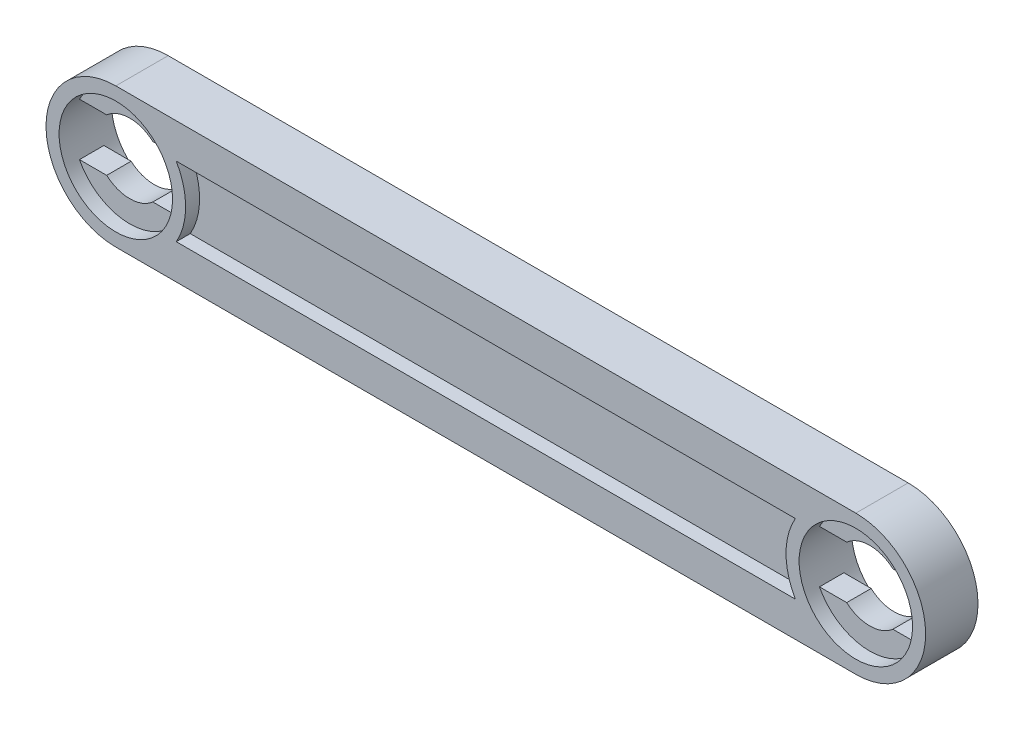
SolidWorks part; units mm, degrees
ref_plane "前视基准面" through (0, 0, 0) normal (0, 0, 1) x (1, 0, 0)
ref_plane "上视基准面" through (0, 0, 0) normal (0, 1, 0) x (1, 0, 0)
ref_plane "右视基准面" through (0, 0, 0) normal (1, 0, 0) x (0, 0, -1)
sketch "草图1" plane through (0, 0, 0) normal (0, 0, 1) x (1, 0, 0)
  line L1 (0, 4) -> (42.4, 4)
  line L3 (0, -4) -> (42.4, -4)
  arc A0 (0, 4) -> (0, -4) centre (0, 0) ccw
  arc A1 (42.4, -4) -> (42.4, 4) centre (42.4, 0) ccw
  dimension "D1" = 42.4
  dimension "D2" = 4
  dimension "D4" = 4
  dimension "D3" = 42.4
extrude "凸台-拉伸1" add sketch "草图1" against normal blind 3
sketch "草图2" plane through (0, 0, 0) normal (0, 0, 1) x (1, 0, 0)
  line L0 (1.3229, -1.5) -> (2.8831, -1.5)
  line L1 (-2.8831, -1.5) -> (-1.3229, -1.5)
  line L2 (1.3229, 1.5) -> (2.8831, 1.5)
  line L3 (-2.8831, 1.5) -> (-1.3229, 1.5)
  arc A0 (1.3229, 1.5) -> (-1.3229, 1.5) centre (0, 0) ccw
  arc A1 (-2.8831, 1.5) -> (-2.8831, -1.5) centre (0, 0) ccw
  arc A3 (2.8831, -1.5) -> (2.8831, 1.5) centre (0, 0) ccw
  arc A4 (-1.3229, -1.5) -> (1.3229, -1.5) centre (0, 0) ccw
extrude "切除-拉伸1" cut sketch "草图2" against normal up to next
sketch "草图3" plane through (0, 0, 0) normal (0, 0, 1) x (1, 0, 0)
  circle A1 centre (0, 0) radius 3.25
extrude "切除-拉伸2" cut sketch "草图3" against normal blind 0.8
extrude "切除-拉伸3" cut sketch "草图3<2>" along normal blind 0.8 from offset 3 offset against normal yes
sketch "草图3<2>" plane through (0, 0, 0) normal (0, 0, 1) x (1, 0, 0) same geometry as "草图3"
pattern_linear "阵列(线性)1" count 2 spacing 42.4 along (1, 0, 0) of "切除-拉伸1", "切除-拉伸2", "切除-拉伸3"
sketch "草图4" plane through (0, 0, 0) normal (0, 0, 1) x (1, 0, 0)
  line L1 (3.4641, -2) -> (38.9359, -2)
  line L3 (3.4641, 2) -> (38.9359, 2)
  arc A0 (3.4641, -2) -> (3.4641, 2) centre (0, 0) ccw
  arc A1 (38.9359, 2) -> (38.9359, -2) centre (42.4, 0) ccw
extrude "切除-拉伸4" cut sketch "草图4" against normal blind 0.8
sketch "草图5" plane through (0, 0, -3) normal (0, 0, -1) x (-1, 0, 0)
  line L0 (-38.4, -2) -> (-38.4, 2)
  line L1 (-4, -2) -> (-4, 2)
  line L2 (-38.4, 2) -> (-4, 2)
  line L3 (-38.4, 0) -> (-4, 0) construction
  line L4 (-38.4, -2) -> (-4, -2)
  circle A0 centre (-42.4, 0) radius 4 construction
  circle A1 centre (0, 0) radius 4 construction
  dimension "D1" = 2
  dimension "D2" = 2
extrude "切除-拉伸5" cut sketch "草图5" against normal blind 0.8
